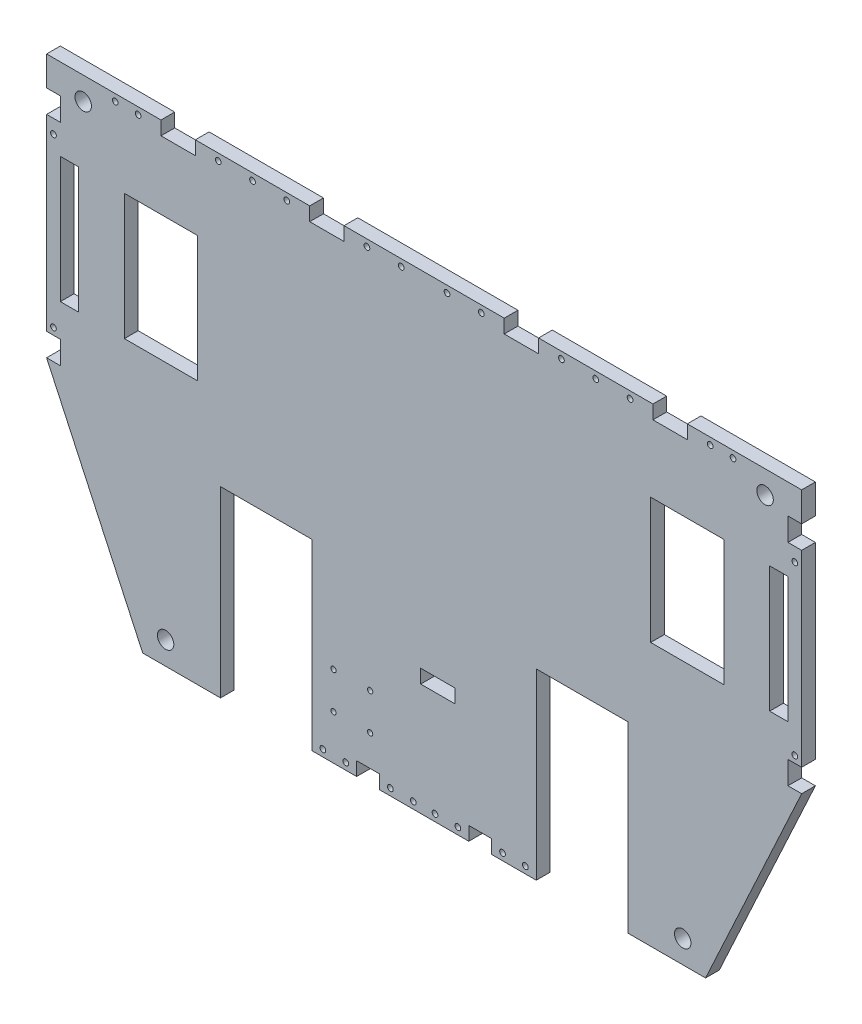
SolidWorks part; units mm, degrees
ref_plane "Plan de face" through (0, 0, 0) normal (0, 0, 1) x (1, 0, 0)
ref_plane "Plan de dessus" through (0, 0, 0) normal (0, 1, 0) x (1, 0, 0)
ref_plane "Plan de droite" through (0, 0, 0) normal (1, 0, 0) x (0, 0, -1)
sketch "Esquisse1" plane through (0, 0, 0) normal (0, 0, 1) x (1, 0, 0)
  line L0 (0, 124.9429) -> (0, -204.46) construction
  line L1 (-165, 96.73) -> (165, 96.73)
  line L2 (165, 96.73) -> (165, -18.27)
  line L3 (165, -18.27) -> (123, -109.0224)
  line L4 (123, -109.0224) -> (-123, -109.0224)
  line L5 (-211.9802, 0) -> (248.5953, 0) construction
  line L6 (-123, -109.0224) -> (-165, -18.27)
  line L7 (-165, -18.27) -> (-165, 96.73)
  line L9 (13.5, -54.0224) -> (-1.5, -54.0224)
  line L10 (13.5, -54.0224) -> (13.5, -60.0224)
  line L11 (13.5, -60.0224) -> (-1.5, -60.0224)
  line L12 (-1.5, -54.0224) -> (-1.5, -60.0224)
  circle A0 centre (-23.6, -89.5224) radius 1.15
  circle A1 centre (-23.6, -73.5224) radius 1.15
  circle A2 centre (-39.6, -89.5224) radius 1.15
  circle A3 centre (-39.6, -73.5224) radius 1.15
  dimension "D15" = 2.3
  dimension "D16" = 2.3
  dimension "D17" = 2.3
  dimension "D18" = 2.3
  dimension "D24" = 83.4
  dimension "D2" = 165
  dimension "D3" = 330
  dimension "D4" = 100
  dimension "D5" = 115
  dimension "D6" = 100
  dimension "D7" = 246
  dimension "D8" = 205.7524
  dimension "D9" = 96.73
  dimension "D10" = 115
  dimension "D11" = 6
  dimension "D12" = 15
  dimension "D13" = 49
  dimension "D14" = 109.5
  dimension "D19" = 19.5
  dimension "D20" = 16
  dimension "D21" = 16
  dimension "D22" = 16
  dimension "D23" = 16
extrude "Boss.-Extru.1" add sketch "Esquisse1" along normal blind 6
sketch "Esquisse2" plane through (0, 0, 6) normal (0, 0, 1) x (1, 0, 0)
  line L0 (-123, -109.0224) -> (123, -109.0224) construction
  line L1 (-159, 60.9776) -> (-151, 60.9776)
  line L2 (-159, 60.9776) -> (-159, 5.9776)
  line L3 (-159, 5.9776) -> (-151, 5.9776)
  line L4 (-151, 60.9776) -> (-151, 5.9776)
  line L5 (-131, 60.9776) -> (-99, 60.9776)
  line L6 (-131, 60.9776) -> (-131, 5.9776)
  line L7 (-131, 5.9776) -> (-99, 5.9776)
  line L8 (-99, 60.9776) -> (-99, 5.9776)
  line L9 (0, 145.0258) -> (0, -189.2208) construction
  line L10 (99, 60.9776) -> (99, 5.9776)
  line L11 (131, 5.9776) -> (99, 5.9776)
  line L12 (131, 60.9776) -> (131, 5.9776)
  line L13 (131, 60.9776) -> (99, 60.9776)
  line L14 (151, 60.9776) -> (151, 5.9776)
  line L15 (159, 5.9776) -> (151, 5.9776)
  line L16 (159, 60.9776) -> (159, 5.9776)
  line L17 (159, 60.9776) -> (151, 60.9776)
  line L19 (89, -109.0224) -> (89, -29.0224)
  line L20 (-49, -109.0224) -> (-89, -109.0224)
  line L21 (-49, -109.0224) -> (-49, -29.0224)
  line L22 (-49, -29.0224) -> (-89, -29.0224)
  line L23 (-89, -109.0224) -> (-89, -29.0224)
  line L24 (49, -29.0224) -> (89, -29.0224)
  line L25 (49, -109.0224) -> (49, -29.0224)
  line L26 (49, -109.0224) -> (89, -109.0224)
  line L27 (-165, 96.73) -> (-165, -18.27) construction
  line L28 (-123, -109.0224) -> (123, -109.0224) construction
  line L29 (165, -18.27) -> (165, 96.73) construction
  line L30 (165, 96.73) -> (-165, 96.73) construction
  circle A0 centre (149, 86.73) radius 3.6
  circle A1 centre (113, -99.0224) radius 3.6
  circle A2 centre (-149, 86.73) radius 3.6
  circle A3 centre (-113, -99.0224) radius 3.6
  dimension "D16" = 7.2
  dimension "D17" = 7.2
  dimension "D18" = 10
  dimension "D19" = 10
  dimension "D20" = 16
  dimension "D21" = 10
  dimension "D2" = 8
  dimension "D3" = 20
  dimension "D4" = 32
  dimension "D5" = 99
  dimension "D6" = 55
  dimension "D7" = 55
  dimension "D8" = 115
  dimension "D9" = 115
  dimension "D10" = 40
  dimension "D11" = 80
  dimension "D12" = 76
  dimension "D13" = 98
  dimension "D14" = 6
extrude "Enlèv. mat.-Extru.1" cut sketch "Esquisse2" against normal blind 6
sketch "Esquisse3" plane through (0, 0, 0) normal (0, 0, -1) x (-1, 0, 0)
  line L0 (165, 96.73) -> (165, -18.27) construction
  line L1 (165, -18.27) -> (159, -18.27)
  line L2 (165, -18.27) -> (165, -8.27)
  line L3 (165, -8.27) -> (159, -8.27)
  line L4 (159, -18.27) -> (159, -8.27)
  line L5 (49, -109.0224) -> (-49, -109.0224) construction
  line L6 (165, 73.8526) -> (159, 73.8526)
  line L7 (165, 73.8526) -> (165, 83.8526)
  line L8 (165, 83.8526) -> (159, 83.8526)
  line L9 (159, 73.8526) -> (159, 83.8526)
  line L10 (29.5, -109.0224) -> (19.5, -109.0224)
  line L11 (29.5, -109.0224) -> (29.5, -103.0224)
  line L12 (29.5, -103.0224) -> (19.5, -103.0224)
  line L13 (19.5, -109.0224) -> (19.5, -103.0224)
  line L14 (49, -109.0224) -> (49, -29.0224) construction
  line L15 (0, -209.4812) -> (0, 177.1799) construction
  line L17 (151, 60.9776) -> (159, 60.9776) construction
  line L18 (-19.5, -109.0224) -> (-19.5, -103.0224)
  line L19 (-29.5, -103.0224) -> (-19.5, -103.0224)
  line L20 (-29.5, -109.0224) -> (-29.5, -103.0224)
  line L21 (-29.5, -109.0224) -> (-19.5, -109.0224)
  line L22 (-159, 73.8526) -> (-159, 83.8526)
  line L23 (-165, 83.8526) -> (-159, 83.8526)
  line L24 (-165, 73.8526) -> (-165, 83.8526)
  line L25 (-165, 73.8526) -> (-159, 73.8526)
  line L26 (-159, -18.27) -> (-159, -8.27)
  line L27 (-165, -8.27) -> (-159, -8.27)
  line L28 (-165, -18.27) -> (-165, -8.27)
  line L29 (-165, -18.27) -> (-159, -18.27)
  line L30 (-165, 96.73) -> (165, 96.73) construction
  line L31 (115, 96.73) -> (100, 96.73)
  line L32 (115, 96.73) -> (115, 90.73)
  line L33 (115, 90.73) -> (100, 90.73)
  line L34 (100, 96.73) -> (100, 90.73)
  line L35 (-35, 96.73) -> (-35, 90.73)
  line L36 (50, 96.73) -> (35, 96.73)
  line L37 (50, 96.73) -> (50, 90.73)
  line L38 (50, 90.73) -> (35, 90.73)
  line L39 (35, 96.73) -> (35, 90.73)
  line L40 (-50, 90.73) -> (-35, 90.73)
  line L41 (-50, 96.73) -> (-50, 90.73)
  line L42 (-50, 96.73) -> (-35, 96.73)
  line L43 (-100, 96.73) -> (-100, 90.73)
  line L44 (-115, 90.73) -> (-100, 90.73)
  line L45 (-115, 96.73) -> (-115, 90.73)
  line L46 (-115, 96.73) -> (-100, 96.73)
  dimension "D1" = 10
  dimension "D2" = 6
  dimension "D3" = 6
  dimension "D4" = 10
  dimension "D5" = 10
  dimension "D6" = 6
  dimension "D7" = 19.5
  dimension "D9" = 12.875
  dimension "D10" = 15
  dimension "D11" = 15
  dimension "D12" = 50
  dimension "D13" = 50
  dimension "D14" = 6
extrude "Enlèv. mat.-Extru.2" cut sketch "Esquisse3" against normal blind 6
sketch "Esquisse4" plane through (0, 0, 0) normal (0, 0, -1) x (-1, 0, 0)
  line L0 (159, 73.8526) -> (165, 73.8526) construction
  line L2 (54.0695, -106.0224) -> (4.75, -106.0224) construction
  line L3 (49, -109.0224) -> (29.5, -109.0224) construction
  line L4 (49, -109.0224) -> (49, -29.0224) construction
  line L5 (19.5, -103.0224) -> (19.5, -109.0224) construction
  line L8 (165, 73.8526) -> (165, -8.27) construction
  line L11 (143.8632, 93.73) -> (10, 93.73) construction
  line L12 (50, 96.73) -> (100, 96.73) construction
  line L13 (115, 90.73) -> (115, 96.73) construction
  line L14 (100, 96.73) -> (100, 90.73) construction
  line L15 (50, 90.73) -> (50, 96.73) construction
  line L16 (35, 96.73) -> (35, 90.73) construction
  line L17 (0, 142.2997) -> (0, -202.2086) construction
  line L18 (-143.8632, 93.73) -> (-10, 93.73) construction
  line L19 (-54.0695, -106.0224) -> (-4.75, -106.0224) construction
  line L21 (165, -8.27) -> (159, -8.27) construction
  circle A0 centre (162, -5.27) radius 1.25
  circle A2 centre (162, 67.8526) radius 1.25
  circle A6 centre (44.25, -106.0224) radius 1.25
  circle A7 centre (14.75, -106.0224) radius 1.25
  circle A8 centre (4.75, -106.0224) radius 1.25
  circle A9 centre (34.2497, -106.0224) radius 1.25
  circle A10 centre (135, 93.73) radius 1.25
  circle A11 centre (125, 93.73) radius 1.25
  circle A12 centre (90, 93.73) radius 1.25
  circle A13 centre (75, 93.73) radius 1.25
  circle A14 centre (60, 93.73) radius 1.25
  circle A15 centre (25, 93.73) radius 1.25
  circle A16 centre (10, 93.73) radius 1.25
  circle A17 centre (-10, 93.73) radius 1.25
  circle A18 centre (-25, 93.73) radius 1.25
  circle A19 centre (-60, 93.73) radius 1.25
  circle A20 centre (-75, 93.73) radius 1.25
  circle A21 centre (-90, 93.73) radius 1.25
  circle A22 centre (-125, 93.73) radius 1.25
  circle A23 centre (-135, 93.73) radius 1.25
  circle A24 centre (-34.2497, -106.0224) radius 1.25
  circle A25 centre (-4.75, -106.0224) radius 1.25
  circle A26 centre (-14.75, -106.0224) radius 1.25
  circle A27 centre (-44.25, -106.0224) radius 1.25
  circle A31 centre (-162, 67.8526) radius 1.25
  circle A33 centre (-162, -5.27) radius 1.25
  dimension "D3" = 2.5
  dimension "D10" = 2.5
  dimension "D11" = 2.5
  dimension "D12" = 2.5
  dimension "D13" = 2.5
  dimension "D14" = 10.0003
  dimension "D18" = 3
  dimension "D19" = 2.5
  dimension "D29" = 2.5
  dimension "D30" = 2.5
  dimension "D31" = 2.5
  dimension "D32" = 2.5
  dimension "D33" = 2.5
  dimension "D34" = 2.5
  dimension "D35" = 2.5
  dimension "D40" = 10
  dimension "D5" = 3
  dimension "D6" = 6
  dimension "D9" = 3
  dimension "D15" = 4.75
  dimension "D16" = 10
  dimension "D17" = 4.75
  dimension "D26" = 3
  dimension "D28" = 3
  dimension "D36" = 10
  dimension "D37" = 10
  dimension "D38" = 10
  dimension "D39" = 15
  dimension "D41" = 15
  dimension "D42" = 10
extrude "Enlèv. mat.-Extru.3" cut sketch "Esquisse4" against normal blind 6
